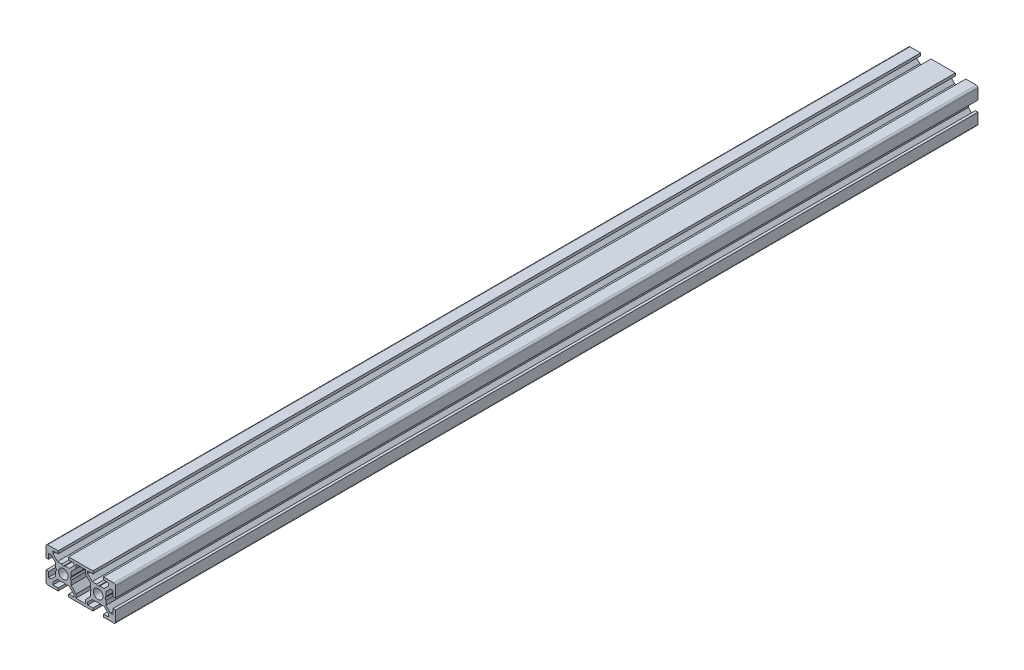
SolidWorks part; units mm, degrees
ref_plane "Front Plane" through (0, 0, 0) normal (0, 0, 1) x (1, 0, 0)
ref_plane "Top Plane" through (0, 0, 0) normal (0, 1, 0) x (1, 0, 0)
ref_plane "Right Plane" through (0, 0, 0) normal (1, 0, 0) x (0, 0, -1)
sketch "Sketch1" plane through (0, 0, 0) normal (0, 0, 1) x (1, 0, 0)
  line L0 (-707.1068, -707.1068) -> (34648.2323, 34648.2323) construction
  line L1 (-3.0018, 10) -> (-10, 10)
  line L2 (0.9376, 4.4579) -> (-0.0011, 3.9339)
  line L3 (3.4252, 4.4579) -> (0.9376, 4.4579)
  line L4 (6.0128, 7.0454) -> (3.4252, 4.4579)
  line L5 (0, -1000) -> (0, 49000) construction
  line L6 (-1000, 0) -> (49000, 0) construction
  line L7 (6.0128, 8.5) -> (6.0128, 7.0454)
  line L8 (3.0018, 8.5) -> (6.0128, 8.5)
  line L9 (3.0018, 10) -> (16.9982, 10)
  line L10 (3.0018, 8.5) -> (3.0018, 10)
  line L11 (-707.1068, 707.1068) -> (34648.2323, -34648.2323) construction
  line L12 (-7.0458, 6.0144) -> (-4.4582, 3.4268)
  line L13 (-8.5008, 6.0144) -> (-7.0458, 6.0144)
  line L14 (-8.5008, 3.0018) -> (-8.5008, 6.0144)
  line L15 (0, -0.0423) -> (0.0002, 2.0704) construction
  line L16 (-10, 3.0018) -> (-10, 10)
  line L17 (-8.5008, 3.0018) -> (-10, 3.0018)
  line L18 (7.2087, -6.4198) -> (7.2087, -8.5)
  line L19 (7.2087, -8.5) -> (12.7913, -8.5)
  line L20 (7.2087, 6.1776) -> (7.2087, 8.5)
  line L21 (7.2087, 8.5) -> (12.7913, 8.5)
  line L22 (7.2087, 6.1776) -> (4.4583, 3.4262)
  line L23 (-3.0018, 8.5) -> (-3.0018, 10)
  line L24 (-3.0018, 8.5) -> (-6.0148, 8.5)
  line L25 (-6.0148, 8.5) -> (-6.0148, 7.0458)
  line L26 (-6.0148, 7.0458) -> (-3.4272, 4.4582)
  line L27 (-3.4272, 4.4582) -> (-0.9396, 4.4582)
  line L28 (-0.9396, 4.4582) -> (-0.0011, 3.9339)
  line L29 (-4.4582, 3.4268) -> (-4.4582, 0.9396)
  line L30 (-4.4582, 0.9396) -> (-3.9347, 0)
  line L31 (4.4575, 0.9396) -> (3.9347, 0)
  line L32 (4.4583, 3.4262) -> (4.4575, 0.9396)
  line L33 (10, -990) -> (10, 49010) construction
  line L34 (19.0624, -4.4579) -> (20.0011, -3.9339)
  line L35 (16.5748, -4.4579) -> (19.0624, -4.4579)
  line L36 (13.9872, -7.0454) -> (16.5748, -4.4579)
  line L37 (-0.9396, -4.4582) -> (-0.0011, -3.9339)
  line L38 (13.9872, -8.5) -> (13.9872, -7.0454)
  line L39 (16.9982, -8.5) -> (13.9872, -8.5)
  line L40 (16.9982, -8.5) -> (16.9982, -10)
  line L41 (24.4575, -0.9396) -> (23.9347, 0)
  line L42 (24.4582, -3.4268) -> (24.4575, -0.9396)
  line L43 (27.0458, -6.0144) -> (24.4582, -3.4268)
  line L44 (28.5008, -6.0144) -> (27.0458, -6.0144)
  line L45 (-3.4272, -4.4582) -> (-0.9396, -4.4582)
  line L46 (-6.0148, -7.0458) -> (-3.4272, -4.4582)
  line L47 (-6.0148, -8.5) -> (-6.0148, -7.0458)
  line L48 (-3.0018, -8.5) -> (-6.0148, -8.5)
  line L49 (-3.0018, -10) -> (-10, -10)
  line L50 (-3.0018, -8.5) -> (-3.0018, -10)
  line L51 (4.4588, -0.9386) -> (3.9347, 0)
  line L52 (4.4583, -3.4262) -> (4.4588, -0.9386)
  line L53 (7.2087, -6.4198) -> (4.4583, -3.4262)
  line L54 (28.5008, -3.0018) -> (28.5008, -6.0144)
  line L55 (30, -3.0018) -> (30, -10)
  line L56 (28.5008, -3.0018) -> (30, -3.0018)
  line L57 (12.7913, -6.4198) -> (15.5417, -3.4262)
  line L58 (-8.5008, -3.0018) -> (-10, -3.0018)
  line L59 (-10, -3.0018) -> (-10, -10)
  line L60 (-8.5008, -3.0018) -> (-8.5008, -6.0144)
  line L61 (-8.5008, -6.0144) -> (-7.0458, -6.0144)
  line L62 (-7.0458, -6.0144) -> (-4.4582, -3.4268)
  line L63 (-4.4582, -3.4268) -> (-4.4575, -0.9396)
  line L64 (-4.4575, -0.9396) -> (-3.9347, 0)
  line L65 (3.0018, -8.5) -> (3.0018, -10)
  line L66 (3.0018, -10) -> (16.9982, -10)
  line L67 (3.0018, -8.5) -> (6.0128, -8.5)
  line L68 (6.0128, -8.5) -> (6.0128, -7.0454)
  line L69 (6.0128, -7.0454) -> (3.4252, -4.4579)
  line L70 (3.4252, -4.4579) -> (0.9376, -4.4579)
  line L71 (0.9376, -4.4579) -> (-0.0011, -3.9339)
  line L72 (15.5417, -3.4262) -> (15.5412, -0.9386)
  line L73 (15.5412, -0.9386) -> (16.0653, 0)
  line L74 (23.0018, -8.5) -> (23.0018, -10)
  line L75 (23.0018, -10) -> (30, -10)
  line L76 (23.0018, -8.5) -> (26.0148, -8.5)
  line L77 (26.0148, -8.5) -> (26.0148, -7.0458)
  line L78 (26.0148, -7.0458) -> (23.4272, -4.4582)
  line L79 (23.4272, -4.4582) -> (20.9396, -4.4582)
  line L80 (20.9396, -4.4582) -> (20.0011, -3.9339)
  line L81 (15.5417, 3.4262) -> (15.5425, 0.9396)
  line L82 (15.5425, 0.9396) -> (16.0653, 0)
  line L83 (24.4582, 0.9396) -> (23.9347, 0)
  line L84 (24.4582, 3.4268) -> (24.4582, 0.9396)
  line L85 (20.9396, 4.4582) -> (20.0011, 3.9339)
  line L86 (23.4272, 4.4582) -> (20.9396, 4.4582)
  line L87 (26.0148, 7.0458) -> (23.4272, 4.4582)
  line L88 (26.0148, 8.5) -> (26.0148, 7.0458)
  line L89 (23.0018, 8.5) -> (26.0148, 8.5)
  line L90 (23.0018, 8.5) -> (23.0018, 10)
  line L91 (12.7913, 6.1776) -> (15.5417, 3.4262)
  line L92 (12.7913, 6.1776) -> (12.7913, 8.5)
  line L93 (12.7913, -6.4198) -> (12.7913, -8.5)
  line L94 (28.5008, 3.0018) -> (30, 3.0018)
  line L95 (30, 3.0018) -> (30, 10)
  line L96 (28.5008, 3.0018) -> (28.5008, 6.0144)
  line L97 (28.5008, 6.0144) -> (27.0458, 6.0144)
  line L98 (27.0458, 6.0144) -> (24.4582, 3.4268)
  line L99 (16.9982, 8.5) -> (16.9982, 10)
  line L100 (16.9982, 8.5) -> (13.9872, 8.5)
  line L101 (13.9872, 8.5) -> (13.9872, 7.0454)
  line L102 (13.9872, 7.0454) -> (16.5748, 4.4579)
  line L103 (16.5748, 4.4579) -> (19.0624, 4.4579)
  line L104 (19.0624, 4.4579) -> (20.0011, 3.9339)
  line L105 (23.0018, 10) -> (30, 10)
  circle A0 centre (0, 0) radius 2.75
  circle A1 centre (20, 0) radius 2.75
  point P76 (10, -10)
  point P79 (10, -10)
  point P88 (10, -3.0018)
  point P111 (10, 8.5)
  point P112 (10, -8.5)
  point P114 (10, 3.0018)
  point P120 (10, 10)
  point P121 (10, 10)
extrude "Boss-Extrude1" add sketch "Sketch1" along normal blind 496
fillet "Fillet2" radius 1 1 edges at (-10, -10, 248) type face fillet first side face at (-10, -6.5009, 248) second side face at (-6.5009, -10, 248)
fillet "Fillet4" radius 1 1 edges at (-10, 10, 248) type face fillet first side face at (-6.5009, 10, 248) second side face at (-10, 6.5009, 248)
fillet "Fillet5" radius 1 1 edges at (30, 10, 248) type face fillet first side face at (26.5009, 10, 248) second side face at (30, 6.5009, 248)
fillet "Fillet6" radius 1 1 edges at (30, -10, 248) type face fillet first side face at (30, -6.5009, 248) second side face at (26.5009, -10, 248)
